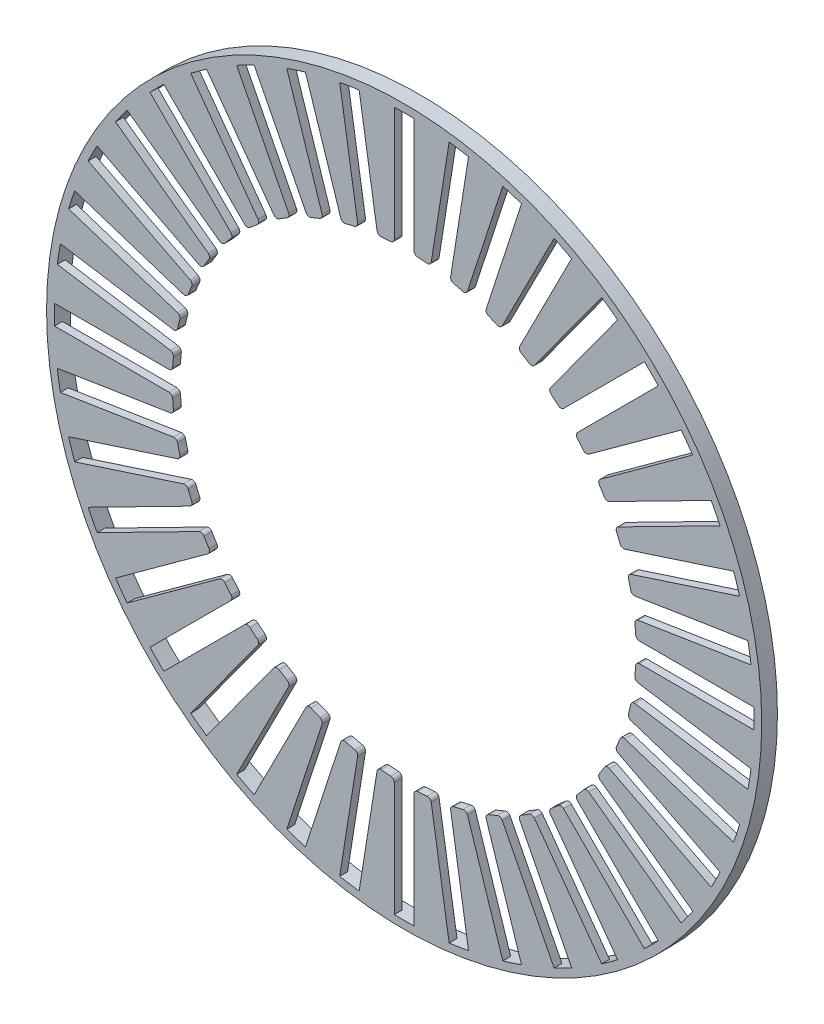
SolidWorks part; units mm, degrees
ref_plane "Plan de face" through (0, 0, 0) normal (0, 0, 1) x (1, 0, 0)
ref_plane "Plan de dessus" through (0, 0, 0) normal (0, 1, 0) x (1, 0, 0)
ref_plane "Plan de droite" through (0, 0, 0) normal (1, 0, 0) x (0, 0, -1)
sketch "Esquisse1" plane through (0, 0, 0) normal (0, 0, 1) x (1, 0, 0)
  line L0 (0, 0) -> (0, 91) construction
  line L1 (11.448, 88.2607) -> (6.7521, 58.6124)
  line L2 (-2.5, 88.9649) -> (2.5, 88.9649)
  line L3 (-2.5, 88.9649) -> (-2.5, 58.947)
  line L4 (-2.5, 58.947) -> (2.5, 58.947)
  line L5 (2.5, 88.9649) -> (2.5, 58.947)
  line L6 (11.448, 88.2607) -> (16.3864, 87.4785)
  line L7 (16.3864, 87.4785) -> (11.6906, 57.8302)
  line L8 (6.7521, 58.6124) -> (11.6906, 57.8302)
  line L161 (25.114, 85.3832) -> (15.838, 56.8345)
  line L162 (25.114, 85.3832) -> (29.8693, 83.8381)
  line L163 (29.8693, 83.8381) -> (20.5933, 55.2894)
  line L164 (15.838, 56.8345) -> (20.5933, 55.2894)
  line L165 (38.1617, 80.4033) -> (24.5339, 53.6571)
  line L166 (38.1617, 80.4033) -> (42.6167, 78.1333)
  line L167 (42.6167, 78.1333) -> (28.9889, 51.3872)
  line L168 (24.5339, 53.6571) -> (28.9889, 51.3872)
  line L169 (50.2697, 73.4436) -> (32.6256, 49.1586)
  line L170 (50.2697, 73.4436) -> (54.3148, 70.5046)
  line L171 (54.3148, 70.5046) -> (36.6707, 46.2197)
  line L172 (32.6256, 49.1586) -> (36.6707, 46.2197)
  line L173 (61.1399, 64.6754) -> (39.9141, 43.4496)
  line L174 (61.1399, 64.6754) -> (64.6754, 61.1399)
  line L175 (64.6754, 61.1399) -> (43.4496, 39.9141)
  line L176 (39.9141, 43.4496) -> (43.4496, 39.9141)
  line L177 (70.5046, 54.3148) -> (46.2197, 36.6707)
  line L178 (70.5046, 54.3148) -> (73.4436, 50.2697)
  line L179 (73.4436, 50.2697) -> (49.1586, 32.6256)
  line L180 (46.2197, 36.6707) -> (49.1586, 32.6256)
  line L181 (78.1333, 42.6167) -> (51.3872, 28.9889)
  line L182 (78.1333, 42.6167) -> (80.4033, 38.1617)
  line L183 (80.4033, 38.1617) -> (53.6571, 24.5339)
  line L184 (51.3872, 28.9889) -> (53.6571, 24.5339)
  line L185 (83.8381, 29.8693) -> (55.2894, 20.5933)
  line L186 (83.8381, 29.8693) -> (85.3832, 25.114)
  line L187 (85.3832, 25.114) -> (56.8345, 15.838)
  line L188 (55.2894, 20.5933) -> (56.8345, 15.838)
  line L189 (87.4785, 16.3864) -> (57.8302, 11.6906)
  line L190 (87.4785, 16.3864) -> (88.2607, 11.448)
  line L191 (88.2607, 11.448) -> (58.6124, 6.7521)
  line L192 (57.8302, 11.6906) -> (58.6124, 6.7521)
  line L193 (88.9649, 2.5) -> (58.947, 2.5)
  line L194 (88.9649, 2.5) -> (88.9649, -2.5)
  line L195 (88.9649, -2.5) -> (58.947, -2.5)
  line L196 (58.947, 2.5) -> (58.947, -2.5)
  line L197 (88.2607, -11.448) -> (58.6124, -6.7521)
  line L198 (88.2607, -11.448) -> (87.4785, -16.3864)
  line L199 (87.4785, -16.3864) -> (57.8302, -11.6906)
  line L200 (58.6124, -6.7521) -> (57.8302, -11.6906)
  line L201 (85.3832, -25.114) -> (56.8345, -15.838)
  line L202 (85.3832, -25.114) -> (83.8381, -29.8693)
  line L203 (83.8381, -29.8693) -> (55.2894, -20.5933)
  line L204 (56.8345, -15.838) -> (55.2894, -20.5933)
  line L205 (80.4033, -38.1617) -> (53.6571, -24.5339)
  line L206 (80.4033, -38.1617) -> (78.1333, -42.6167)
  line L207 (78.1333, -42.6167) -> (51.3872, -28.9889)
  line L208 (53.6571, -24.5339) -> (51.3872, -28.9889)
  line L209 (73.4436, -50.2697) -> (49.1586, -32.6256)
  line L210 (73.4436, -50.2697) -> (70.5046, -54.3148)
  line L211 (70.5046, -54.3148) -> (46.2197, -36.6707)
  line L212 (49.1586, -32.6256) -> (46.2197, -36.6707)
  line L213 (64.6754, -61.1399) -> (43.4496, -39.9141)
  line L214 (64.6754, -61.1399) -> (61.1399, -64.6754)
  line L215 (61.1399, -64.6754) -> (39.9141, -43.4496)
  line L216 (43.4496, -39.9141) -> (39.9141, -43.4496)
  line L217 (54.3148, -70.5046) -> (36.6707, -46.2197)
  line L218 (54.3148, -70.5046) -> (50.2697, -73.4436)
  line L219 (50.2697, -73.4436) -> (32.6256, -49.1586)
  line L220 (36.6707, -46.2197) -> (32.6256, -49.1586)
  line L221 (42.6167, -78.1333) -> (28.9889, -51.3872)
  line L222 (42.6167, -78.1333) -> (38.1617, -80.4033)
  line L223 (38.1617, -80.4033) -> (24.5339, -53.6571)
  line L224 (28.9889, -51.3872) -> (24.5339, -53.6571)
  line L225 (29.8693, -83.8381) -> (20.5933, -55.2894)
  line L226 (29.8693, -83.8381) -> (25.114, -85.3832)
  line L227 (25.114, -85.3832) -> (15.838, -56.8345)
  line L228 (20.5933, -55.2894) -> (15.838, -56.8345)
  line L229 (16.3864, -87.4785) -> (11.6906, -57.8302)
  line L230 (16.3864, -87.4785) -> (11.448, -88.2607)
  line L231 (11.448, -88.2607) -> (6.7521, -58.6124)
  line L232 (11.6906, -57.8302) -> (6.7521, -58.6124)
  line L233 (2.5, -88.9649) -> (2.5, -58.947)
  line L234 (2.5, -88.9649) -> (-2.5, -88.9649)
  line L235 (-2.5, -88.9649) -> (-2.5, -58.947)
  line L236 (2.5, -58.947) -> (-2.5, -58.947)
  line L237 (-11.448, -88.2607) -> (-6.7521, -58.6124)
  line L238 (-11.448, -88.2607) -> (-16.3864, -87.4785)
  line L239 (-16.3864, -87.4785) -> (-11.6906, -57.8302)
  line L240 (-6.7521, -58.6124) -> (-11.6906, -57.8302)
  line L241 (-25.114, -85.3832) -> (-15.838, -56.8345)
  line L242 (-25.114, -85.3832) -> (-29.8693, -83.8381)
  line L243 (-29.8693, -83.8381) -> (-20.5933, -55.2894)
  line L244 (-15.838, -56.8345) -> (-20.5933, -55.2894)
  line L245 (-38.1617, -80.4033) -> (-24.5339, -53.6571)
  line L246 (-38.1617, -80.4033) -> (-42.6167, -78.1333)
  line L247 (-42.6167, -78.1333) -> (-28.9889, -51.3872)
  line L248 (-24.5339, -53.6571) -> (-28.9889, -51.3872)
  line L249 (-50.2697, -73.4436) -> (-32.6256, -49.1586)
  line L250 (-50.2697, -73.4436) -> (-54.3148, -70.5046)
  line L251 (-54.3148, -70.5046) -> (-36.6707, -46.2197)
  line L252 (-32.6256, -49.1586) -> (-36.6707, -46.2197)
  line L253 (-61.1399, -64.6754) -> (-39.9141, -43.4496)
  line L254 (-61.1399, -64.6754) -> (-64.6754, -61.1399)
  line L255 (-64.6754, -61.1399) -> (-43.4496, -39.9141)
  line L256 (-39.9141, -43.4496) -> (-43.4496, -39.9141)
  line L257 (-70.5046, -54.3148) -> (-46.2197, -36.6707)
  line L258 (-70.5046, -54.3148) -> (-73.4436, -50.2697)
  line L259 (-73.4436, -50.2697) -> (-49.1586, -32.6256)
  line L260 (-46.2197, -36.6707) -> (-49.1586, -32.6256)
  line L261 (-78.1333, -42.6167) -> (-51.3872, -28.9889)
  line L262 (-78.1333, -42.6167) -> (-80.4033, -38.1617)
  line L263 (-80.4033, -38.1617) -> (-53.6571, -24.5339)
  line L264 (-51.3872, -28.9889) -> (-53.6571, -24.5339)
  line L265 (-83.8381, -29.8693) -> (-55.2894, -20.5933)
  line L266 (-83.8381, -29.8693) -> (-85.3832, -25.114)
  line L267 (-85.3832, -25.114) -> (-56.8345, -15.838)
  line L268 (-55.2894, -20.5933) -> (-56.8345, -15.838)
  line L269 (-87.4785, -16.3864) -> (-57.8302, -11.6906)
  line L270 (-87.4785, -16.3864) -> (-88.2607, -11.448)
  line L271 (-88.2607, -11.448) -> (-58.6124, -6.7521)
  line L272 (-57.8302, -11.6906) -> (-58.6124, -6.7521)
  line L273 (-88.9649, -2.5) -> (-58.947, -2.5)
  line L274 (-88.9649, -2.5) -> (-88.9649, 2.5)
  line L275 (-88.9649, 2.5) -> (-58.947, 2.5)
  line L276 (-58.947, -2.5) -> (-58.947, 2.5)
  line L277 (-88.2607, 11.448) -> (-58.6124, 6.7521)
  line L278 (-88.2607, 11.448) -> (-87.4785, 16.3864)
  line L279 (-87.4785, 16.3864) -> (-57.8302, 11.6906)
  line L280 (-58.6124, 6.7521) -> (-57.8302, 11.6906)
  line L281 (-85.3832, 25.114) -> (-56.8345, 15.838)
  line L282 (-85.3832, 25.114) -> (-83.8381, 29.8693)
  line L283 (-83.8381, 29.8693) -> (-55.2894, 20.5933)
  line L284 (-56.8345, 15.838) -> (-55.2894, 20.5933)
  line L285 (-80.4033, 38.1617) -> (-53.6571, 24.5339)
  line L286 (-80.4033, 38.1617) -> (-78.1333, 42.6167)
  line L287 (-78.1333, 42.6167) -> (-51.3872, 28.9889)
  line L288 (-53.6571, 24.5339) -> (-51.3872, 28.9889)
  line L289 (-73.4436, 50.2697) -> (-49.1586, 32.6256)
  line L290 (-73.4436, 50.2697) -> (-70.5046, 54.3148)
  line L291 (-70.5046, 54.3148) -> (-46.2197, 36.6707)
  line L292 (-49.1586, 32.6256) -> (-46.2197, 36.6707)
  line L293 (-64.6754, 61.1399) -> (-43.4496, 39.9141)
  line L294 (-64.6754, 61.1399) -> (-61.1399, 64.6754)
  line L295 (-61.1399, 64.6754) -> (-39.9141, 43.4496)
  line L296 (-43.4496, 39.9141) -> (-39.9141, 43.4496)
  line L297 (-54.3148, 70.5046) -> (-36.6707, 46.2197)
  line L298 (-54.3148, 70.5046) -> (-50.2697, 73.4436)
  line L299 (-50.2697, 73.4436) -> (-32.6256, 49.1586)
  line L300 (-36.6707, 46.2197) -> (-32.6256, 49.1586)
  line L301 (-42.6167, 78.1333) -> (-28.9889, 51.3872)
  line L302 (-42.6167, 78.1333) -> (-38.1617, 80.4033)
  line L303 (-38.1617, 80.4033) -> (-24.5339, 53.6571)
  line L304 (-28.9889, 51.3872) -> (-24.5339, 53.6571)
  line L305 (-29.8693, 83.8381) -> (-20.5933, 55.2894)
  line L306 (-29.8693, 83.8381) -> (-25.114, 85.3832)
  line L307 (-25.114, 85.3832) -> (-15.838, 56.8345)
  line L308 (-20.5933, 55.2894) -> (-15.838, 56.8345)
  line L309 (-16.3864, 87.4785) -> (-11.6906, 57.8302)
  line L310 (-16.3864, 87.4785) -> (-11.448, 88.2607)
  line L311 (-11.448, 88.2607) -> (-6.7521, 58.6124)
  line L312 (-11.6906, 57.8302) -> (-6.7521, 58.6124)
  circle A0 centre (0, 0) radius 89
  circle A1 centre (0, 0) radius 91
  circle A2 centre (0, 0) radius 59
  arc A3 (-2.5, 59.947) -> (-3.5, 58.8961) centre (-3.5, 59.8973) cw
  arc A4 (2.5, 59.947) -> (3.5, 58.8961) centre (3.5, 59.8973) ccw
  arc A5 (11.847, 58.8179) -> (12.6703, 57.6235) centre (12.8269, 58.6124) ccw
  arc A6 (6.9086, 59.6) -> (5.7565, 58.7185) centre (5.9131, 59.7074) cw
  arc A7 (20.9023, 56.2405) -> (21.5286, 54.932) centre (21.838, 55.8842) ccw
  arc A8 (16.147, 57.7855) -> (14.8712, 57.0951) centre (15.1806, 58.0473) cw
  arc A9 (29.4429, 52.2782) -> (29.8568, 50.8878) centre (30.3113, 51.7799) ccw
  arc A10 (24.9879, 54.5482) -> (23.6197, 54.0658) centre (24.0743, 54.9579) cw
  arc A11 (37.2585, 47.0287) -> (37.4498, 45.5907) centre (38.0383, 46.4007) ccw
  arc A12 (33.2134, 49.9676) -> (31.7867, 49.7052) centre (32.3752, 50.5152) cw
  arc A13 (44.1567, 40.6212) -> (44.1207, 39.171) centre (44.8287, 39.8789) ccw
  arc A14 (40.6212, 44.1567) -> (39.171, 44.1207) centre (39.8789, 44.8287) cw
  arc A15 (49.9676, 33.2134) -> (49.7052, 31.7867) centre (50.5152, 32.3752) ccw
  arc A16 (47.0287, 37.2585) -> (45.5907, 37.4498) centre (46.4007, 38.0383) cw
  arc A17 (54.5482, 24.9879) -> (54.0658, 23.6197) centre (54.9579, 24.0743) ccw
  arc A18 (52.2782, 29.4429) -> (50.8878, 29.8568) centre (51.7799, 30.3113) cw
  arc A19 (57.7855, 16.147) -> (57.0951, 14.8712) centre (58.0473, 15.1806) ccw
  arc A20 (56.2405, 20.9023) -> (54.932, 21.5286) centre (55.8842, 21.838) cw
  arc A21 (59.6, 6.9086) -> (58.7185, 5.7565) centre (59.7074, 5.9131) ccw
  arc A22 (58.8179, 11.847) -> (57.6235, 12.6703) centre (58.6124, 12.8269) cw
  arc A23 (59.947, -2.5) -> (58.8961, -3.5) centre (59.8973, -3.5) ccw
  arc A24 (59.947, 2.5) -> (58.8961, 3.5) centre (59.8973, 3.5) cw
  arc A25 (58.8179, -11.847) -> (57.6235, -12.6703) centre (58.6124, -12.8269) ccw
  arc A26 (59.6, -6.9086) -> (58.7185, -5.7565) centre (59.7074, -5.9131) cw
  arc A27 (56.2405, -20.9023) -> (54.932, -21.5286) centre (55.8842, -21.838) ccw
  arc A28 (57.7855, -16.147) -> (57.0951, -14.8712) centre (58.0473, -15.1806) cw
  arc A29 (52.2782, -29.4429) -> (50.8878, -29.8568) centre (51.7799, -30.3113) ccw
  arc A30 (54.5482, -24.9879) -> (54.0658, -23.6197) centre (54.9579, -24.0743) cw
  arc A31 (47.0287, -37.2585) -> (45.5907, -37.4498) centre (46.4007, -38.0383) ccw
  arc A32 (49.9676, -33.2134) -> (49.7052, -31.7867) centre (50.5152, -32.3752) cw
  arc A33 (40.6212, -44.1567) -> (39.171, -44.1207) centre (39.8789, -44.8287) ccw
  arc A34 (44.1567, -40.6212) -> (44.1207, -39.171) centre (44.8287, -39.8789) cw
  arc A35 (33.2134, -49.9676) -> (31.7867, -49.7052) centre (32.3752, -50.5152) ccw
  arc A36 (37.2585, -47.0287) -> (37.4498, -45.5907) centre (38.0383, -46.4007) cw
  arc A37 (24.9879, -54.5482) -> (23.6197, -54.0658) centre (24.0743, -54.9579) ccw
  arc A38 (29.4429, -52.2782) -> (29.8568, -50.8878) centre (30.3113, -51.7799) cw
  arc A39 (16.147, -57.7855) -> (14.8712, -57.0951) centre (15.1806, -58.0473) ccw
  arc A40 (20.9023, -56.2405) -> (21.5286, -54.932) centre (21.838, -55.8842) cw
  arc A41 (6.9086, -59.6) -> (5.7565, -58.7185) centre (5.9131, -59.7074) ccw
  arc A42 (11.847, -58.8179) -> (12.6703, -57.6235) centre (12.8269, -58.6124) cw
  arc A43 (-2.5, -59.947) -> (-3.5, -58.8961) centre (-3.5, -59.8973) ccw
  arc A44 (2.5, -59.947) -> (3.5, -58.8961) centre (3.5, -59.8973) cw
  arc A45 (-11.847, -58.8179) -> (-12.6703, -57.6235) centre (-12.8269, -58.6124) ccw
  arc A46 (-6.9086, -59.6) -> (-5.7565, -58.7185) centre (-5.9131, -59.7074) cw
  arc A47 (-20.9023, -56.2405) -> (-21.5286, -54.932) centre (-21.838, -55.8842) ccw
  arc A48 (-16.147, -57.7855) -> (-14.8712, -57.0951) centre (-15.1806, -58.0473) cw
  arc A49 (-29.4429, -52.2782) -> (-29.8568, -50.8878) centre (-30.3113, -51.7799) ccw
  arc A50 (-24.9879, -54.5482) -> (-23.6197, -54.0658) centre (-24.0743, -54.9579) cw
  arc A51 (-37.2585, -47.0287) -> (-37.4498, -45.5907) centre (-38.0383, -46.4007) ccw
  arc A52 (-33.2134, -49.9676) -> (-31.7867, -49.7052) centre (-32.3752, -50.5152) cw
  arc A53 (-44.1567, -40.6212) -> (-44.1207, -39.171) centre (-44.8287, -39.8789) ccw
  arc A54 (-40.6212, -44.1567) -> (-39.171, -44.1207) centre (-39.8789, -44.8287) cw
  arc A55 (-49.9676, -33.2134) -> (-49.7052, -31.7867) centre (-50.5152, -32.3752) ccw
  arc A56 (-47.0287, -37.2585) -> (-45.5907, -37.4498) centre (-46.4007, -38.0383) cw
  arc A57 (-54.5482, -24.9879) -> (-54.0658, -23.6197) centre (-54.9579, -24.0743) ccw
  arc A58 (-52.2782, -29.4429) -> (-50.8878, -29.8568) centre (-51.7799, -30.3113) cw
  arc A59 (-57.7855, -16.147) -> (-57.0951, -14.8712) centre (-58.0473, -15.1806) ccw
  arc A60 (-56.2405, -20.9023) -> (-54.932, -21.5286) centre (-55.8842, -21.838) cw
  arc A61 (-59.6, -6.9086) -> (-58.7185, -5.7565) centre (-59.7074, -5.9131) ccw
  arc A62 (-58.8179, -11.847) -> (-57.6235, -12.6703) centre (-58.6124, -12.8269) cw
  arc A63 (-59.947, 2.5) -> (-58.8961, 3.5) centre (-59.8973, 3.5) ccw
  arc A64 (-59.947, -2.5) -> (-58.8961, -3.5) centre (-59.8973, -3.5) cw
  arc A65 (-58.8179, 11.847) -> (-57.6235, 12.6703) centre (-58.6124, 12.8269) ccw
  arc A66 (-59.6, 6.9086) -> (-58.7185, 5.7565) centre (-59.7074, 5.9131) cw
  arc A67 (-56.2405, 20.9023) -> (-54.932, 21.5286) centre (-55.8842, 21.838) ccw
  arc A68 (-57.7855, 16.147) -> (-57.0951, 14.8712) centre (-58.0473, 15.1806) cw
  arc A69 (-52.2782, 29.4429) -> (-50.8878, 29.8568) centre (-51.7799, 30.3113) ccw
  arc A70 (-54.5482, 24.9879) -> (-54.0658, 23.6197) centre (-54.9579, 24.0743) cw
  arc A71 (-47.0287, 37.2585) -> (-45.5907, 37.4498) centre (-46.4007, 38.0383) ccw
  arc A72 (-49.9676, 33.2134) -> (-49.7052, 31.7867) centre (-50.5152, 32.3752) cw
  arc A73 (-40.6212, 44.1567) -> (-39.171, 44.1207) centre (-39.8789, 44.8287) ccw
  arc A74 (-44.1567, 40.6212) -> (-44.1207, 39.171) centre (-44.8287, 39.8789) cw
  arc A75 (-33.2134, 49.9676) -> (-31.7867, 49.7052) centre (-32.3752, 50.5152) ccw
  arc A76 (-37.2585, 47.0287) -> (-37.4498, 45.5907) centre (-38.0383, 46.4007) cw
  arc A77 (-24.9879, 54.5482) -> (-23.6197, 54.0658) centre (-24.0743, 54.9579) ccw
  arc A78 (-29.4429, 52.2782) -> (-29.8568, 50.8878) centre (-30.3113, 51.7799) cw
  arc A79 (-16.147, 57.7855) -> (-14.8712, 57.0951) centre (-15.1806, 58.0473) ccw
  arc A80 (-20.9023, 56.2405) -> (-21.5286, 54.932) centre (-21.838, 55.8842) cw
  arc A81 (-6.9086, 59.6) -> (-5.7565, 58.7185) centre (-5.9131, 59.7074) ccw
  arc A82 (-11.847, 58.8179) -> (-12.6703, 57.6235) centre (-12.8269, 58.6124) cw
  point P12 (0, 88.9649)
  point P13 (0, 58.947)
  point P173 (0, 0)
  point P414 (0, 0)
  dimension "D1" = 178
  dimension "D4" = 5
  dimension "D5" = 40
  dimension "D6" = 1
  dimension "D7" = 1
  dimension "D8" = 1
  dimension "D9" = 1
  dimension "D10" = 1
  dimension "D11" = 1
  dimension "D2" = 2
  dimension "D3" = 30
  dimension "D12" = 40
extrude "Boss.-Extru.1" add sketch "Esquisse1" along normal blind 2 contours A2 L169 A0 L167 | A2 L165 A0 L163 | A2 L161 A0 L7 | A2 L1 A0 L5 | A2 L3 A0 L311 | A2 L309 A0 L307 | A2 L305 A0 L303 | A2 L301 A0 L299 | A2 L297 A0 L295 | A2 L293 A0 L291 | A2 L289 A0 L287 | A2 L285 A0 L283 | A2 L281 A0 L279 | A2 L277 A0 L275 | A2 L273 A0 L271 | A2 L269 A0 L267 | A2 L265 A0 L263 | A2 L261 A0 L259 | A2 L257 A0 L255 | A2 L253 A0 L251 | A2 L249 A0 L247 | A2 L245 A0 L243 | A2 L241 A0 L239 | A2 L237 A0 L235 | A2 L233 A0 L231 | A2 L229 A0 L227 | A2 L225 A0 L223 | A2 L221 A0 L219 | A2 L217 A0 L215 | A2 L213 A0 L211 | A2 L209 A0 L207 | A2 L205 A0 L203 | A2 L201 A0 L199 | A2 L197 A0 L195 | A2 L193 A0 L191 | A2 L189 A0 L187 | A2 L185 A0 L183 | A2 L181 A0 L179 | A2 L177 A0 L175 | A2 L173 A0 L171 | A0 L1 region at (5.9459, 75.5504, 0) region at (17.6914, 73.6901, 0) region at (-5.9459, 75.5504, 0) region at (29.0013, 70.0153, 0) region at (-17.6914, 73.6901, 0) region at (39.5971, 64.6165, 0) region at (-29.0013, 70.0153, 0) region at (49.2178, 57.6266, 0) region at (-39.5971, 64.6165, 0) region at (57.6266, 49.2178, 0) region at (-49.2178, 57.6266, 0) region at (64.6165, 39.5971, 0) region at (-57.6266, 49.2178, 0) region at (70.0153, 29.0013, 0) region at (-64.6165, 39.5971, 0) region at (73.6901, 17.6914, 0) region at (-70.0153, 29.0013, 0) region at (75.5504, 5.9459, 0) region at (-73.6901, 17.6914, 0) region at (75.5504, -5.9459, 0) region at (-75.5504, 5.9459, 0) region at (73.6901, -17.6914, 0) region at (-75.5504, -5.9459, 0) region at (70.0153, -29.0013, 0) region at (-73.6901, -17.6914, 0) region at (64.6165, -39.5971, 0) region at (-70.0153, -29.0013, 0) region at (57.6266, -49.2178, 0) region at (-64.6165, -39.5971, 0) region at (49.2178, -57.6266, 0) region at (-57.6266, -49.2178, 0) region at (39.5971, -64.6165, 0) region at (-49.2178, -57.6266, 0) region at (29.0013, -70.0153, 0) region at (-39.5971, -64.6165, 0) region at (17.6914, -73.6901, 0) region at (-29.0013, -70.0153, 0) region at (5.9459, -75.5504, 0) region at (-17.6914, -73.6901, 0) region at (-5.9459, -75.5504, 0) region at (-90.7426, 0, 0)
extrude "Boss.-Extru.2" add sketch "Esquisse1<3>" against normal blind 2 contours A0 region at (-90.7426, 0, 0)
sketch "Esquisse1<3>" plane through (0, 0, 0) normal (0, 0, 1) x (1, 0, 0) same geometry as "Esquisse1"
